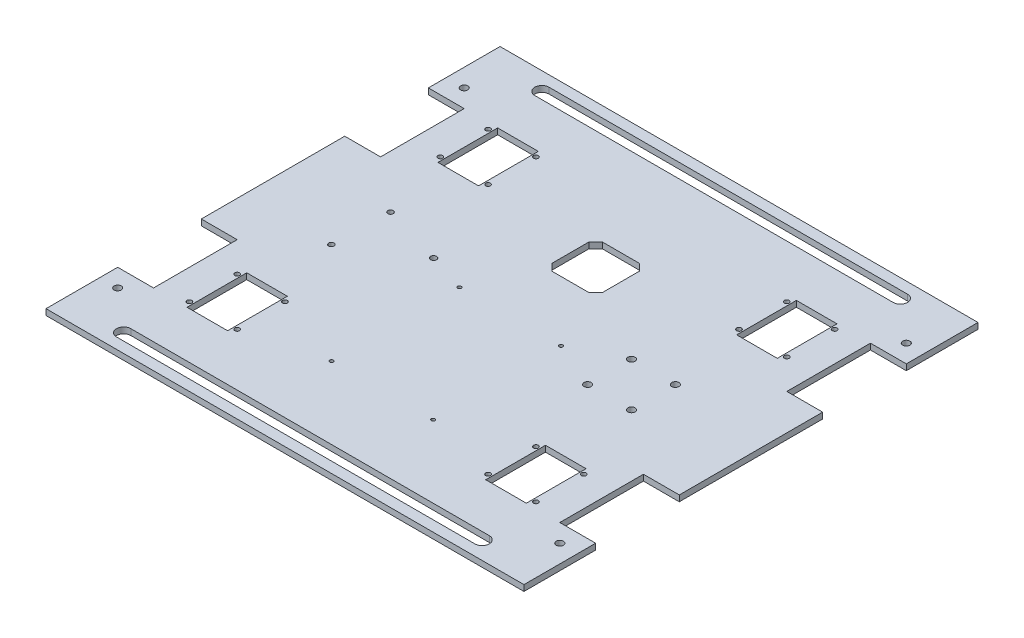
SolidWorks part; units mm, degrees
ref_plane "前基準面" through (0, 0, 0) normal (0, 0, 1) x (1, 0, 0)
ref_plane "上基準面" through (0, 0, 0) normal (0, 1, 0) x (1, 0, 0)
ref_plane "右基準面" through (0, 0, 0) normal (1, 0, 0) x (0, 0, -1)
sketch "草圖1" plane through (0, 0, 0) normal (0, 1, 0) x (1, 0, 0)
  line L0 (200, 190) -> (200, -190)
  line L1 (200, 190) -> (-200, 190)
  line L3 (200, -190) -> (-200, -190)
  line L4 (-200, 190) -> (-200, -190)
  line L5 (0, -190) -> (0, 190) construction
  line L6 (200, 0) -> (-200, 0) construction
  line L8 (-200, 130) -> (-200, -130) construction
  line L10 (-170, 130) -> (-170, -130) construction
  line L11 (-200, 130) -> (200, 130) construction
  line L12 (-200, 130) -> (-200, 190) construction
  line L13 (-200, 190) -> (200, 190) construction
  line L15 (-200, -130) -> (200, -130) construction
  line L16 (-200, -130) -> (-200, -190) construction
  line L17 (-200, -190) -> (200, -190) construction
  line L19 (170, 130) -> (170, -130) construction
  point P0 (0, 0)
  dimension "D1" = 400
  dimension "D2" = 260
  dimension "D3" = 60
  dimension "D4" = 60
  dimension "D5" = 30
extrude "填料-伸長1" add sketch "草圖1" along normal blind 5
sketch "草圖2" plane through (0, 5, 0) normal (0, 1, 0) x (1, 0, 0)
  line L0 (200, -190) -> (200, 190) construction
  line L1 (-200, 190) -> (200, 190) construction
  line L5 (-185, 190) -> (-185, -190) construction
  line L21 (-200, 190) -> (200, 190) construction
  line L22 (-200, 190) -> (-200, 130) construction
  line L23 (-200, 130) -> (200, 130) construction
  line L24 (-275.3304, 0) -> (275.3304, 0) construction
  line L25 (0, 247.3454) -> (0, -229.8147) construction
  line L42 (200, 190) -> (200, 130) construction
  line L44 (-155, 35) -> (-72.5, 35) construction
  line L45 (-155, 35) -> (-155, -35) construction
  line L46 (-155, -35) -> (-72.5, -35) construction
  line L47 (-72.5, 35) -> (-72.5, -35) construction
  line L59 (-200, 160) -> (200, 160) construction
  line L60 (-200, 145) -> (200, 145) construction
  line L61 (-200, -145) -> (200, -145) construction
  line L62 (-200, -160) -> (200, -160) construction
  line L63 (-200, -130) -> (200, -130) construction
  line L64 (200, -190) -> (200, -130) construction
  line L65 (-200, -190) -> (200, -190) construction
  line L66 (-200, -190) -> (-200, -130) construction
  line L67 (185, -190) -> (185, 190) construction
  line L68 (-200, 130) -> (-170, 130) construction
  line L69 (-200, 130) -> (-200, -130) construction
  line L70 (-200, -130) -> (-170, -130) construction
  line L71 (-170, 130) -> (-170, -130) construction
  line L72 (200, 130) -> (170, 130) construction
  line L73 (200, 130) -> (200, -130) construction
  line L74 (200, -130) -> (170, -130) construction
  line L75 (170, 130) -> (170, -130) construction
  line L76 (170, -60) -> (200, -60)
  line L77 (-200, 130) -> (-170, 130)
  line L78 (-200, 130) -> (-200, 60)
  line L79 (-200, 60) -> (-170, 60)
  line L80 (-170, 130) -> (-170, 60)
  line L81 (-170, -130) -> (-200, -130)
  line L82 (-170, -130) -> (-170, -60)
  line L83 (-170, -60) -> (-200, -60)
  line L84 (-200, -130) -> (-200, -60)
  line L85 (200, -130) -> (200, -60)
  line L86 (170, -130) -> (200, -130)
  line L87 (170, -130) -> (170, -60)
  line L88 (200, 60) -> (170, 60)
  line L89 (170, 130) -> (170, 60)
  line L90 (200, 130) -> (170, 130)
  line L91 (200, 130) -> (200, 60)
  line L100 (100, -80) -> (150, -80) construction
  line L101 (78.65, 21.35) -> (121.35, 21.35) construction
  line L102 (78.65, 21.35) -> (78.65, -21.35) construction
  line L103 (78.65, -21.35) -> (121.35, -21.35) construction
  line L104 (121.35, 21.35) -> (121.35, -21.35) construction
  line L105 (-150, -80) -> (-100, -80) construction
  line L106 (-150, -80) -> (-150, -130) construction
  line L107 (-150, -130) -> (-100, -130) construction
  line L108 (-100, -80) -> (-100, -130) construction
  line L109 (-142, -80) -> (-108, -80)
  line L110 (-142, -80) -> (-142, -130)
  line L111 (-142, -130) -> (-108, -130)
  line L112 (-108, -80) -> (-108, -130)
  line L113 (100, -80) -> (100, -130) construction
  line L114 (100, -130) -> (150, -130) construction
  line L115 (150, -80) -> (150, -130) construction
  line L116 (108, -80) -> (142, -80)
  line L117 (108, -80) -> (108, -130)
  line L118 (108, -130) -> (142, -130)
  line L119 (142, -80) -> (142, -130)
  line L120 (-150, 130) -> (-100, 130) construction
  line L121 (-150, 130) -> (-150, 80) construction
  line L122 (-150, 80) -> (-100, 80) construction
  line L123 (-100, 130) -> (-100, 80) construction
  line L124 (-142, 130) -> (-108, 130)
  line L125 (-142, 130) -> (-142, 80)
  line L126 (-142, 80) -> (-108, 80)
  line L127 (-108, 130) -> (-108, 80)
  line L128 (100, 130) -> (150, 130) construction
  line L129 (100, 130) -> (100, 80) construction
  line L130 (100, 80) -> (150, 80) construction
  line L131 (150, 130) -> (150, 80) construction
  line L132 (108, 130) -> (142, 130)
  line L133 (108, 130) -> (108, 80)
  line L134 (108, 80) -> (142, 80)
  line L135 (142, 130) -> (142, 80)
  line L136 (-21.15, 85.5) -> (-15.5, 91.15)
  line L137 (44, -110) -> (-44, -110) construction
  line L138 (44, -110) -> (44, 0) construction
  line L139 (44, 0) -> (-44, 0) construction
  line L140 (-44, -110) -> (-44, 0) construction
  line L141 (-15.5, 91.15) -> (15.5, 91.15)
  line L142 (-21.15, 85.5) -> (-21.15, 54.5)
  line L143 (-15.5, 48.85) -> (15.5, 48.85)
  line L144 (21.15, 85.5) -> (21.15, 54.5)
  line L145 (15.5, 91.15) -> (21.15, 85.5)
  line L146 (15.5, 48.85) -> (21.15, 54.5)
  line L147 (-21.15, 54.5) -> (-15.5, 48.85)
  line L148 (-234.8869, -145) -> (-234.8869, -175) construction
  line L149 (-214.8869, -145) -> (-214.8869, -175)
  line L150 (-254.8869, -145) -> (-254.8869, -175)
  line L151 (-234.8869, 145) -> (-234.8869, 175) construction
  line L152 (-214.8869, 145) -> (-214.8869, 175)
  line L153 (-254.8869, 145) -> (-254.8869, 175)
  line L154 (234.8869, -145) -> (234.8869, -175) construction
  line L155 (214.8869, -145) -> (214.8869, -175)
  line L156 (254.8869, -145) -> (254.8869, -175)
  line L157 (234.8869, 145) -> (234.8869, 175) construction
  line L158 (214.8869, 145) -> (214.8869, 175)
  line L159 (254.8869, 145) -> (254.8869, 175)
  line L160 (-150, 175) -> (150, 175) construction
  line L161 (-150, 181) -> (150, 181)
  line L162 (-150, 169) -> (150, 169)
  line L163 (-150, -175) -> (150, -175) construction
  line L164 (-150, -181) -> (150, -181)
  line L165 (-150, -169) -> (150, -169)
  circle A21 centre (-127.07, -24.13) radius 2.25
  circle A22 centre (-125.8, 24.13) radius 2.25
  circle A23 centre (-74.5, 8.89) radius 2.5
  circle A32 centre (-185, 145) radius 3
  circle A33 centre (185, 145) radius 3
  circle A34 centre (-185, -145) radius 3
  circle A35 centre (185, -145) radius 3
  circle A40 centre (81.65, 18.35) radius 3
  circle A41 centre (118.35, 18.35) radius 3
  circle A42 centre (81.65, -18.35) radius 3
  circle A43 centre (118.35, -18.35) radius 3
  circle A44 centre (-145, -85) radius 2
  circle A45 centre (-105, -85) radius 2
  circle A46 centre (-145, -125) radius 2
  circle A47 centre (-105, -125) radius 2
  circle A48 centre (105, -85) radius 2
  circle A49 centre (145, -85) radius 2
  circle A50 centre (105, -125) radius 2
  circle A51 centre (145, -125) radius 2
  circle A52 centre (-145, 125) radius 2
  circle A53 centre (-105, 125) radius 2
  circle A54 centre (-145, 85) radius 2
  circle A55 centre (-105, 85) radius 2
  circle A56 centre (105, 125) radius 2
  circle A57 centre (145, 125) radius 2
  circle A58 centre (105, 85) radius 2
  circle A59 centre (145, 85) radius 2
  circle A60 centre (-42.5, -1.5) radius 1.5
  circle A61 centre (42.5, -1.5) radius 1.5
  circle A62 centre (-42.5, -108.5) radius 1.5
  circle A63 centre (42.5, -108.5) radius 1.5
  circle A64 centre (-15.5, 85.5) radius 1.5 construction
  circle A65 centre (15.5, 85.5) radius 1.5 construction
  circle A66 centre (-15.5, 54.5) radius 1.5 construction
  circle A67 centre (15.5, 54.5) radius 1.5 construction
  arc A68 (-214.8869, -145) -> (-254.8869, -145) centre (-234.8869, -145) ccw
  arc A69 (-254.8869, -175) -> (-214.8869, -175) centre (-234.8869, -175) ccw
  arc A70 (-214.8869, 145) -> (-254.8869, 145) centre (-234.8869, 145) cw
  arc A71 (-254.8869, 175) -> (-214.8869, 175) centre (-234.8869, 175) cw
  arc A72 (214.8869, -145) -> (254.8869, -145) centre (234.8869, -145) cw
  arc A73 (254.8869, -175) -> (214.8869, -175) centre (234.8869, -175) cw
  arc A74 (214.8869, 145) -> (254.8869, 145) centre (234.8869, 145) ccw
  arc A75 (254.8869, 175) -> (214.8869, 175) centre (234.8869, 175) ccw
  arc A76 (-150, 181) -> (-150, 169) centre (-150, 175) ccw
  arc A77 (150, 169) -> (150, 181) centre (150, 175) ccw
  arc A78 (-150, -181) -> (-150, -169) centre (-150, -175) cw
  arc A79 (150, -169) -> (150, -181) centre (150, -175) cw
  point P54 (0, 70)
  point P55 (0, 91.15)
  point P56 (-234.8869, -160)
  point P62 (-113.75, 0)
  point P64 (-155, 0)
  point P70 (-234.8869, -125)
  point P71 (-234.8869, -195)
  point P73 (0, 175)
  point P89 (-234.8869, 160)
  point P102 (-113.75, 35)
  point P175 (0, 0)
  point P177 (-44, -55)
  point P182 (0, -55)
  point P183 (100, 21.35)
  point P185 (78.65, 0)
  point P187 (234.8869, -160)
  point P191 (100, 0)
  point P195 (234.8869, 160)
  point P201 (24.8415, 179.9312)
  point P202 (0, 175)
  point P203 (0, 178.4861)
  point P204 (-21.15, 91.15)
  point P205 (21.15, 48.85)
  point P206 (-21.15, 48.85)
  point P207 (21.15, 91.15)
  point P223 (0, 0)
  point P224 (-21.15, 70)
  point P227 (0, -175)
  dimension "D5" = 60
  dimension "D6" = 15
  dimension "D7" = 30
  dimension "D9" = 6
  dimension "D18" = 4.5
  dimension "D25" = 5
  dimension "D28" = 42.7
  dimension "D10" = 6
  dimension "D13" = 70
  dimension "D30" = 6
  dimension "D31" = 50
  dimension "D32" = 50
  dimension "D33" = 40
  dimension "D37" = 4
  dimension "D46" = 4
  dimension "D55" = 4
  dimension "D64" = 4
  dimension "D73" = 3
  dimension "D77" = 3
  dimension "D26" = 6
  dimension "D3" = 15
  dimension "D4" = 15
  dimension "D11" = 70
  dimension "D12" = 40
  dimension "D14" = 120
  dimension "D15" = 200
  dimension "D16" = 82.5
  dimension "D17" = 70
  dimension "D19" = 10.87
  dimension "D20" = 27.93
  dimension "D21" = 29.2
  dimension "D22" = 10.87
  dimension "D23" = 26.11
  dimension "D24" = 2
  dimension "D27" = 15
  dimension "D29" = 42.7
  dimension "D34" = 300
  dimension "D36" = 40
  dimension "D38" = 5
  dimension "D39" = 5
  dimension "D40" = 34
  dimension "D41" = 8
  dimension "D42" = 50
  dimension "D43" = 50
  dimension "D44" = 40
  dimension "D45" = 40
  dimension "D47" = 5
  dimension "D48" = 5
  dimension "D49" = 34
  dimension "D50" = 8
  dimension "D51" = 50
  dimension "D52" = 50
  dimension "D53" = 40
  dimension "D54" = 40
  dimension "D56" = 5
  dimension "D57" = 5
  dimension "D58" = 34
  dimension "D59" = 8
  dimension "D60" = 50
  dimension "D61" = 50
  dimension "D62" = 40
  dimension "D63" = 40
  dimension "D65" = 5
  dimension "D66" = 5
  dimension "D67" = 34
  dimension "D68" = 8
  dimension "D69" = 20
  dimension "D70" = 20
  dimension "D71" = 88
  dimension "D72" = 110
  dimension "D74" = 15
  dimension "D75" = 42.3
  dimension "D76" = 42.3
  dimension "D78" = 31
  dimension "D79" = 31
  dimension "D80" = 5.65
  dimension "D81" = 5.65
  dimension "D82" = 5.65
  dimension "D83" = 5.65
  dimension "D84" = 5.65
  dimension "D85" = 5.65
  dimension "D86" = 5.65
  dimension "D87" = 5.65
  dimension "D88" = 5.65
  dimension "D89" = 5.65
extrude "除料-伸長1" cut sketch "草圖2" against normal through all
